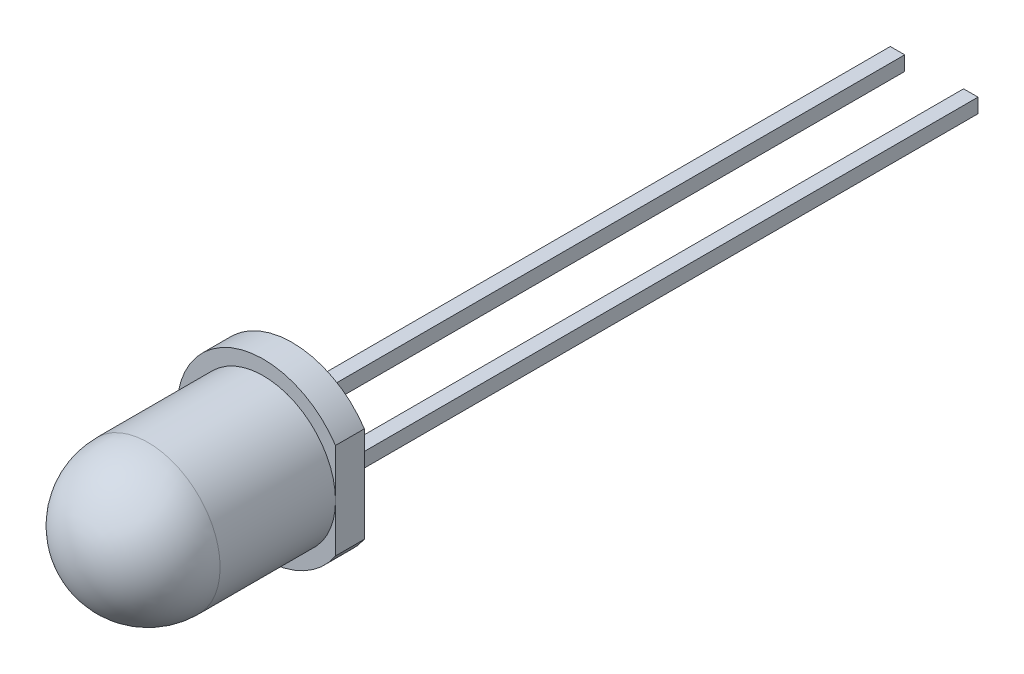
SolidWorks part; units mm, degrees
ref_plane "Front Plane" through (0, 0, 0) normal (0, 0, 1) x (1, 0, 0)
ref_plane "Top Plane" through (0, 0, 0) normal (0, 1, 0) x (1, 0, 0)
ref_plane "Right Plane" through (0, 0, 0) normal (1, 0, 0) x (0, 0, -1)
sketch "Sketch1" plane through (0, 0, 0) normal (0, 0, 1) x (1, 0, 0)
  circle A0 centre (0, 0) radius 3
  dimension "D1" = 6
extrude "Boss-Extrude1" add sketch "Sketch1" along normal blind 1
sketch "Sketch2" plane through (0, 0, 1) normal (0, 0, 1) x (1, 0, 0)
  circle A0 centre (0, 0) radius 2.5
  dimension "D1" = 5
extrude "Boss-Extrude2" add sketch "Sketch2" along normal blind 4
dome "Dome1" faces to dome 1 distance 2.5 reverse direction no elliptical dome no face at (2.5, 0, 5) parameters "D1"=2.5
sketch "Sketch3" plane through (0, 0, 1) normal (0, 0, 1) x (1, 0, 0)
  line L1 (2.5, 1.8503) -> (3, 1.8503)
  line L2 (2.5, 1.8503) -> (2.5, -2.181)
  line L3 (2.5, -2.181) -> (3, -2.181)
  line L4 (3, 1.8503) -> (3, -2.181)
  circle A0 centre (0, 0) radius 3 construction
  circle A1 centre (0, 0) radius 2.5 construction
extrude "Cut-Extrude1" cut sketch "Sketch3" against normal up to next
ref_plane "Plane3" through (0, 0, 0) normal (0, 1, 0) x (1, 0, 0)
sketch "Sketch8" plane through (0, 0, 0) normal (0, 1, 0) x (1, 0, 0)
  line L0 (0, 0) -> (-1.27, 0) construction
  line L1 (2.5, 0) -> (-3, 0) construction
  line L2 (-1.27, 0) -> (-1.27, 22)
  dimension "D1" = 22
  dimension "D2" = 1.27
sheet metal parameters "Sheet-Metal1" thickness 0.5 parameters "D1"=0.1
base flange "Base-Flange1" sketch "Sketch8" end condition mid plane depth 0.5 reverse direction no thickness 0.5 reverse thickness direction no bend radius 0.1
sketch "Sketch9" plane through (0, 0, 0) normal (0, 1, 0) x (1, 0, 0)
  line L0 (1.27, 0) -> (1.27, 22)
  line L1 (-1.27, 22) -> (-0.77, 22) construction
  line L2 (2.5, 0) -> (-3, 0) construction
  dimension "D1" = 1.27
sheet metal parameters "Sheet-Metal2" thickness 0.5 parameters "D1"=0.1
base flange "Base-Flange2" sketch "Sketch9" end condition mid plane depth 0.5 reverse direction no thickness 0.5 reverse thickness direction no bend radius 0.1
sketch "Sketch10" plane through (0, 0, 0) normal (0, 0, -1) x (-1, 0, 0)
  line L0 (0, 0) -> (0, 3) construction
  arc A0 (-2.5, -1.6583) -> (-2.5, 1.6583) centre (0, 0) ccw construction
ref_plane "Plane4" through (0, 0, 0) normal (1, 0, 0) x (0, 0, -1)
flat pattern "Flat-Pattern1" [suppressed]
sketch "Bend-Lines1" plane through (0, 0, 0) normal (0, 1, 0) x (1, 0, 0)
sketch3d "Bounding-Box1" [suppressed]
  line L0 (0, 0.5, 0) -> (4.53, 0.5, 0) construction
  line L1 (0, 0, 0) -> (4.53, 0, 0) construction
  line L2 (0, 0.5, 0) -> (0, 0, 0) construction
  line L3 (4.53, 0.5, 0) -> (4.53, 0, 0) construction
flat pattern "Flat-Pattern2" [suppressed]
sketch "Bend-Lines2" plane through (0, 0, 0) normal (0, 1, 0) x (1, 0, 0)
sketch "Bounding-Box2" [suppressed] plane through (0, 0, 0) normal (0, 1, 0) x (1, 0, 0)
